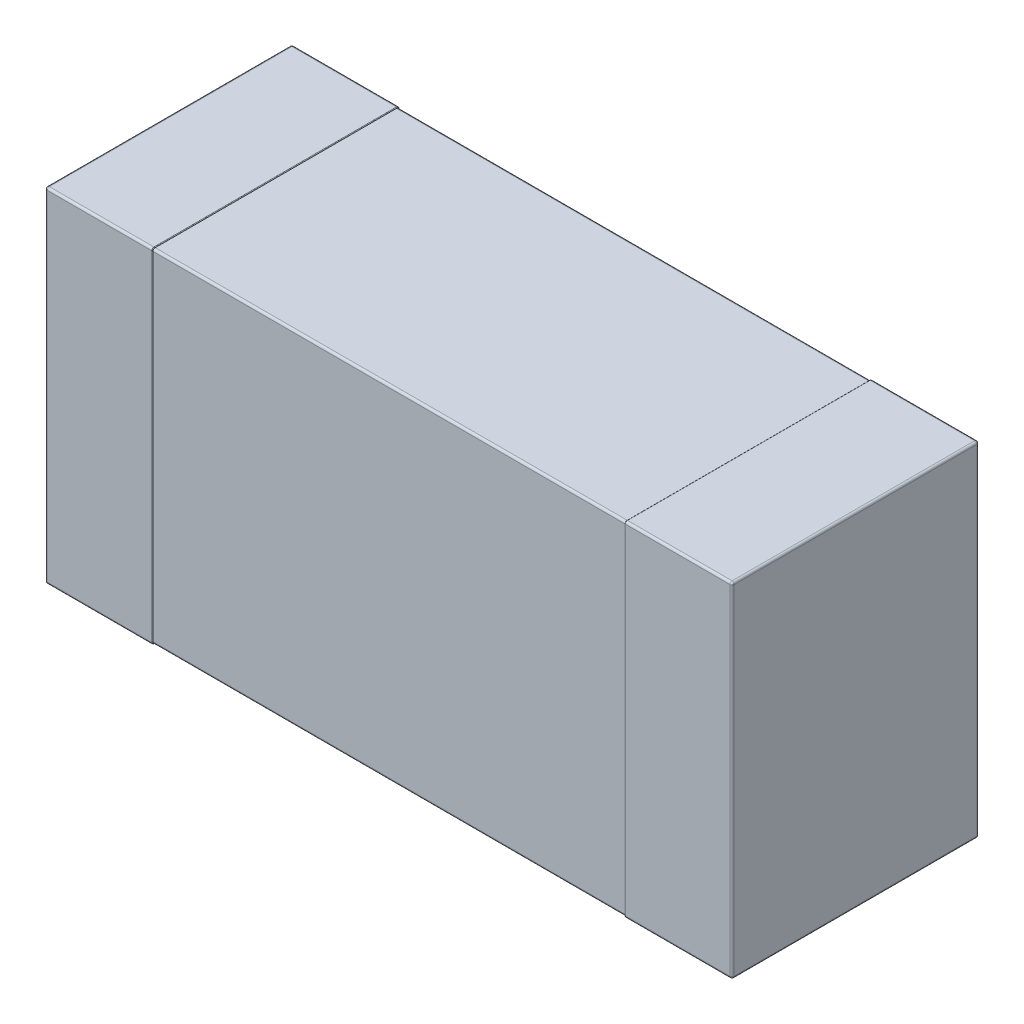
SolidWorks part; units mm, degrees
ref_plane "Top Plane" through (0, 0, 0) normal (0, 0, 1) x (1, 0, 0)
ref_plane "Front Plane" through (0, 0, 0) normal (0, 1, 0) x (1, 0, 0)
ref_plane "Side Plane" through (0, 0, 0) normal (1, 0, 0) x (0, 0, -1)
sketch "Sketch1" plane through (0, 0, 0) normal (0, 0, 1) x (1, 0, 0)
  line L1 (-1.6, 0.8) -> (1.6, 0.8)
  line L2 (-1.6, 0.8) -> (-1.6, -0.8)
  line L3 (-1.6, -0.8) -> (1.6, -0.8)
  line L4 (1.6, 0.8) -> (1.6, -0.8)
  dimension "D1" = 3.2
  dimension "D2" = 1.6
  dimension "D3" = 1.6
  dimension "D4" = 0.8
extrude "All body" add sketch "Sketch1" along normal blind 1.15
sketch "Sketch2" plane through (0, 0, 0) normal (1, 0, 0) x (0, 0, -1)
  line L14 (-0.003, 0.797) -> (-1.147, 0.797)
  line L15 (-0.003, -0.797) -> (-0.003, 0.797)
  line L16 (-1.147, -0.797) -> (-0.003, -0.797)
  line L17 (-1.147, 0.797) -> (-1.147, -0.797)
  line L18 (-0.003, 0.797) -> (-1.147, 0.797)
  line L19 (-0.003, -0.797) -> (-0.003, 0.797)
  line L20 (-1.147, -0.797) -> (-0.003, -0.797)
  line L21 (-1.147, 0.797) -> (-1.147, -0.797)
  dimension "D1" = 0.003
extrude "Cut out the body for pin" cut sketch "Sketch2" against normal blind 1.1 and the other way blind 1.1 flip side to cut
fillet "Body fillet" radius 0.01 4 edges at (0, 0.797, 0.003) (0, 0.797, 1.147) (0, -0.797, 0.003) (0, -0.797, 1.147)
fillet "Pin fillet a" radius 0.01 16 edges at (1.6, -0.8, 0.575) (1.6, 0, 1.15) (1.6, 0.8, 0.575) (1.6, 0, 0) (-1.6, 0.8, 0.575) (-1.6, 0, 1.15) (-1.6, -0.8, 0.575) (-1.6, 0, 0) (1.35, 0.8, 1.15) (1.35, -0.8, 1.15) (1.35, -0.8, 0) (1.35, 0.8, 0) (-1.35, 0.8, 0) (-1.35, -0.8, 0) (-1.35, 0.8, 1.15) (-1.35, -0.8, 1.15)
fillet "Pin fillet b" radius 0.003 16 edges at (1.1, -0.7971, 1.1471) (1.1, -0.8, 0.575) (1.1, -0.7971, 0.0029) (1.1, 0, 0) (1.1, 0.7971, 0.0029) (1.1, 0.8, 0.575) (1.1, 0.7971, 1.1471) (-1.1, -0.7971, 1.1471) (-1.1, -0.8, 0.575) (-1.1, -0.7971, 0.0029) (-1.1, 0, 0) (-1.1, 0.7971, 0.0029) (-1.1, 0.8, 0.575) (-1.1, 0.7971, 1.1471) (1.1, 0, 1.15) (-1.1, 0, 1.15)
